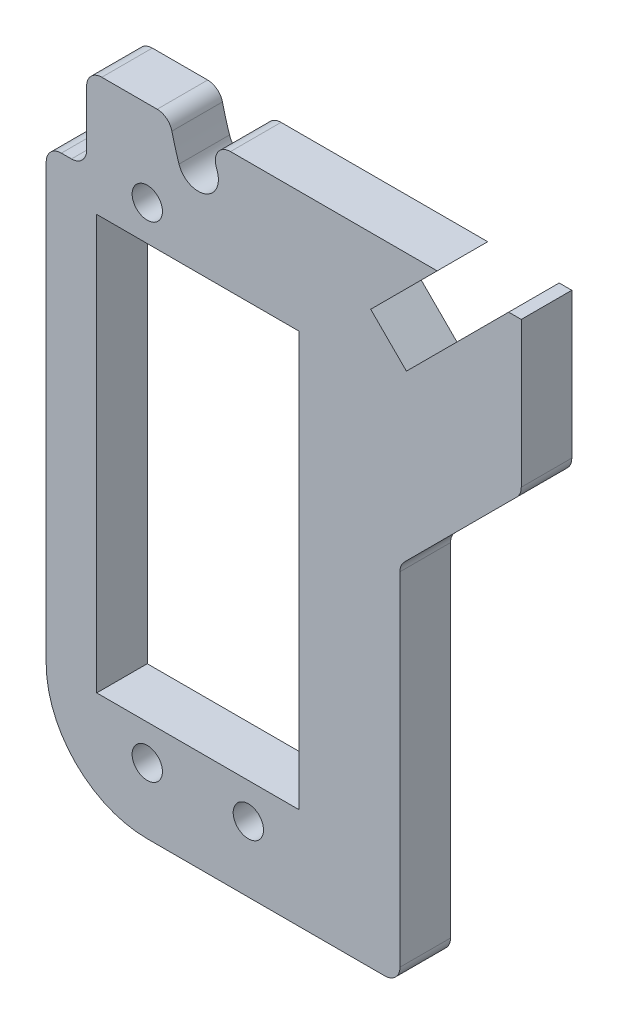
SolidWorks part; units mm, degrees
ref_plane "Plan de face" through (0, 0, 0) normal (0, 0, 1) x (1, 0, 0)
ref_plane "Plan de dessus" through (0, 0, 0) normal (0, 1, 0) x (1, 0, 0)
ref_plane "Plan de droite" through (0, 0, 0) normal (1, 0, 0) x (0, 0, -1)
sketch "Esquisse1" plane through (0, 0, 0) normal (0, 0, 1) x (1, 0, 0)
  line L0 (15, 10) -> (15, 51) construction
  line L1 (0, 0) -> (35, 0)
  line L2 (0, 0) -> (0, 54.5)
  line L3 (4, 63) -> (12.2239, 63)
  line L4 (45.7522, 63) -> (35.6395, 52.8874)
  line L5 (15, 51) -> (5, 51)
  line L6 (16.2735, 63) -> (45.7522, 63)
  line L7 (25, 10) -> (5, 10)
  line L8 (5, 51) -> (5, 10)
  line L9 (5, 30.5) -> (25, 30.5) construction
  line L10 (25, 10) -> (25, 51)
  line L11 (25, 51) -> (15, 51)
  line L12 (32.104, 56.4229) -> (35.6395, 52.8874) construction
  line L13 (47, 48) -> (47, 63)
  line L14 (40.5893, 57.8371) -> (33.5182, 50.7661) construction
  line L15 (35.6395, 52.8874) -> (32.104, 56.4229)
  line L16 (32.104, 56.4229) -> (38.6811, 63)
  line L17 (45.7522, 63) -> (47, 63)
  line L18 (45.7522, 63) -> (16.2735, 63)
  line L19 (16.2735, 63) -> (38.6811, 63)
  line L20 (47, 48) -> (35, 36)
  line L21 (35, 36) -> (35, 0)
  line L22 (0, 54.5) -> (4, 54.5)
  line L23 (4, 63) -> (4, 54.5)
  circle A0 centre (10, 54.5) radius 1.5
  circle A1 centre (20, 54.5) radius 1.5 construction
  circle A2 centre (20, 6.5) radius 1.5
  circle A3 centre (10, 6.5) radius 1.5
  arc A4 (14.2239, 63) -> (15.0389, 60) centre (43.2843, 69.2843) ccw construction
  arc A5 (12.269, 62.5773) -> (13.1389, 59.3755) centre (43.2843, 69.2843) ccw
  arc A6 (16.2735, 63) -> (16.9389, 60.6245) centre (43.2843, 69.2843) ccw
  arc A7 (12.2239, 63) -> (12.269, 62.5773) centre (14.2239, 63) ccw
  arc A8 (13.1389, 59.3755) -> (16.9389, 60.6245) centre (15.0389, 60) ccw
  point P35 (14.7126, 61.0586)
  dimension "D6" = 3.5
  dimension "D8" = 3
  dimension "D14" = 2
  dimension "D15" = 27.7321
  dimension "D16" = 31.7321
  dimension "D20" = 29.7321
  dimension "D1" = 20
  dimension "D2" = 41
  dimension "D3" = 10
  dimension "D4" = 12
  dimension "D5" = 5
  dimension "D7" = 5
  dimension "D9" = 22
  dimension "D10" = 5
  dimension "D12" = 4
  dimension "D13" = 8.5
  dimension "D17" = 1.9548
  dimension "D18" = 10
  dimension "D19" = 15
  dimension "D21" = 3
extrude "Boss.-Extru.1" add sketch "Esquisse1" along normal blind 5 contours L17 L6 L4 L15 L16 L3 L2 L1 L13 L11 L10 L7 L8 L5 A0 A2 A3 region at (0.786, 27.25, 0)
fillet "Congé2" radius 10 1 edges at (0, 0, 2.5)
fillet "Congé4" radius 1.5 8 edges at (0, 54.5, 2.5) (4, 54.5, 2.5) (47, 48, 2.5) (35, 36, 2.5) (35, 0, 2.5) (16.2735, 63, 2.5) (12.2239, 63, 2.5) (4, 63, 2.5)
